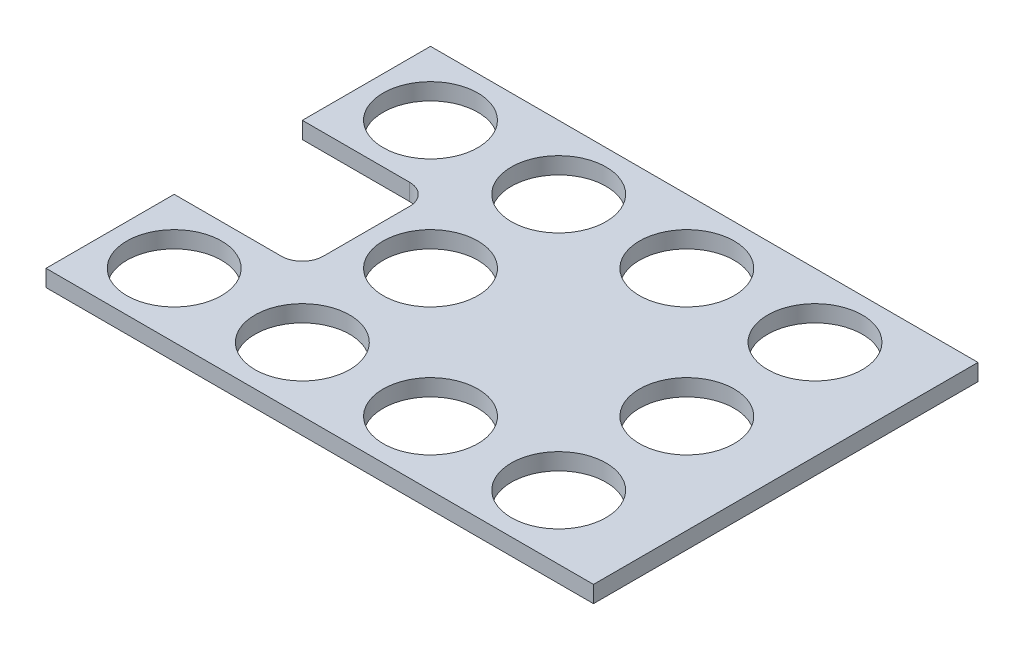
SolidWorks part; units mm, degrees
material "Pine"
ref_plane "Front Plane" through (0, 0, 0) normal (0, 0, 1) x (1, 0, 0)
ref_plane "Top Plane" through (0, 0, 0) normal (0, 1, 0) x (1, 0, 0)
ref_plane "Right Plane" through (0, 0, 0) normal (1, 0, 0) x (0, 0, -1)
sketch "Sketch1" plane through (0, 0, 0) normal (0, 1, 0) x (1, 0, 0)
  line L0 (46, 46) -> (264.076, 46)
  line L1 (0, 0) -> (393, 0)
  line L2 (0, 0) -> (0, 276)
  line L3 (0, 276) -> (393, 276)
  line L4 (393, 0) -> (393, 276)
  line L6 (0, 184) -> (77, 184)
  line L7 (0, 184) -> (0, 92)
  line L8 (0, 92) -> (77, 92)
  line L9 (92, 169) -> (92, 107)
  circle A0 centre (46, 46) radius 34
  circle A1 centre (46, 230) radius 34
  arc A2 (77, 92) -> (92, 107) centre (77, 107) ccw
  arc A3 (77, 184) -> (92, 169) centre (77, 169) cw
  circle A4 centre (138, 138) radius 34
  circle A5 centre (322, 138) radius 34
  dimension "D2" = 68
  dimension "D9" = 15
  dimension "D1" = 46
  dimension "D4" = 276
  dimension "D5" = 46
  dimension "D6" = 46
  dimension "D7" = 46
  dimension "D8" = 92
  dimension "D10" = 92
  dimension "D11" = 92
  dimension "D12" = 138
  dimension "D13" = 138
  dimension "D14" = 184
  dimension "D15" = 138
  dimension "D3" = 393
extrude "Boss-Extrude1" add sketch "Sketch1" along normal blind 12 contours L2 L3 L4 L1
extrude "Cut-Extrude1" cut sketch "Sketch1<3>" along normal up to surface (12 mm away) contours A0 | A1 up to face at (196.5, 12, -138)
sketch "Sketch1<3>" plane through (0, 0, 0) normal (0, 1, 0) x (1, 0, 0) same geometry as "Sketch1"
pattern_linear "LPattern1" count 4 spacing 92 along (1, 0, 0) of "Cut-Extrude1"
extrude "Cut-Extrude3" cut sketch "Sketch1<4>" along normal up to surface (12 mm away) contours A3 L6 L2 L8 A2 L9 | A4 | A5 region at (45.5078, 0, -138) region at (138, 0, -138) region at (322, 0, -138) up to face at (322, 12, -12)
sketch "Sketch1<4>" plane through (0, 0, 0) normal (0, 1, 0) x (1, 0, 0) same geometry as "Sketch1"
equation "\"LENGTH\" = 1000mm"
equation "\"PLY\"= 12mm"
equation "\"D1@Boss-Extrude1\"=\"PLY\""
equation "\"CENTER_BRACE_LENGTH\" = 393mm"
equation "\"D3@Sketch1\"=\"CENTER_BRACE_LENGTH\""
